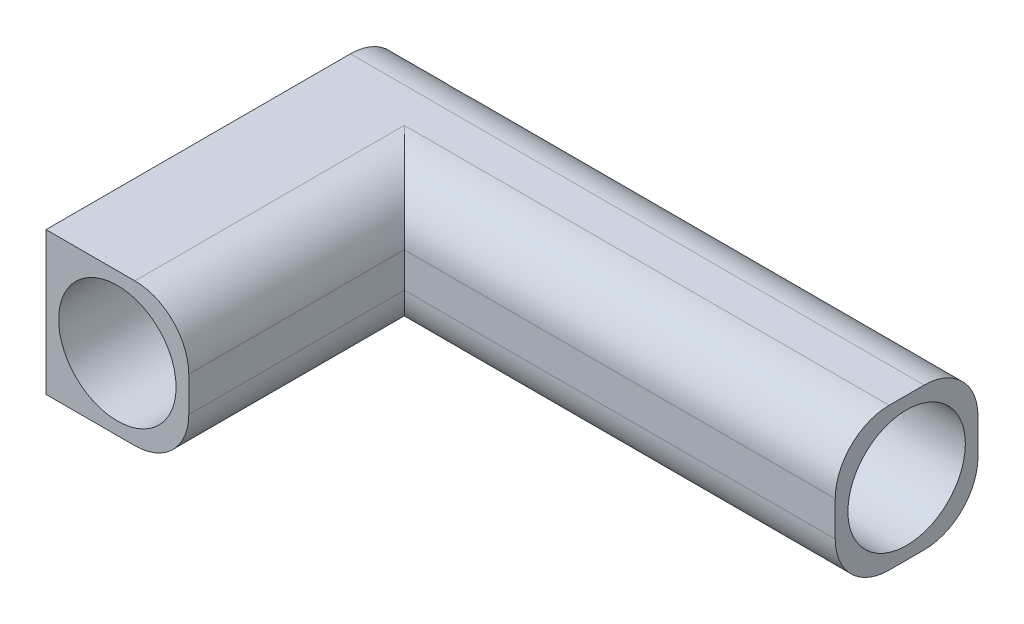
SolidWorks part; units mm, degrees
ref_plane "Front Plane" through (0, 0, 0) normal (0, 0, 1) x (1, 0, 0)
ref_plane "Top Plane" through (0, 0, 0) normal (0, 1, 0) x (1, 0, 0)
ref_plane "Right Plane" through (0, 0, 0) normal (1, 0, 0) x (0, 0, -1)
sketch "Sketch2" plane through (0, 0, 0) normal (0, 1, 0) x (1, 0, 0)
  line L0 (0, 0) -> (0, 66.5)
  line L1 (0, 66.5) -> (106.5, 66.5)
  line L2 (106.5, 66.5) -> (106.5, 40)
  line L3 (106.5, 40) -> (26.5, 40)
  line L4 (26.5, 40) -> (26.5, 0)
  line L5 (26.5, 0) -> (0, 0)
  dimension "D1" = 40
  dimension "D2" = 26.5
  dimension "D3" = 80
extrude "Boss-Extrude1" add sketch "Sketch2" along normal blind 26.5
sketch "Sketch3" plane through (0, 0, 0) normal (0, 0, 1) x (1, 0, 0)
  line L0 (0, 0) -> (26.5, 26.5) construction
  circle A0 centre (13.25, 13.25) radius 10.9
  dimension "D1" = 21.8
extrude "Cut-Extrude1" cut sketch "Sketch3" against normal through all
sketch "Sketch4" plane through (106.5, 0, 0) normal (1, 0, 0) x (0, 0, -1)
  line L0 (40, 26.5) -> (66.5, 0) construction
  circle A0 centre (53.25, 13.25) radius 10.9
  dimension "D1" = 21.8
extrude "Cut-Extrude2" cut sketch "Sketch4" against normal through all
fillet "Fillet1" radius 10 6 edges at (26.5, 26.5, -20) (26.5, 0, -20) (53.25, 26.5, -66.5) (53.25, 0, -66.5) (66.5, 26.5, -40) (66.5, 0, -40)
